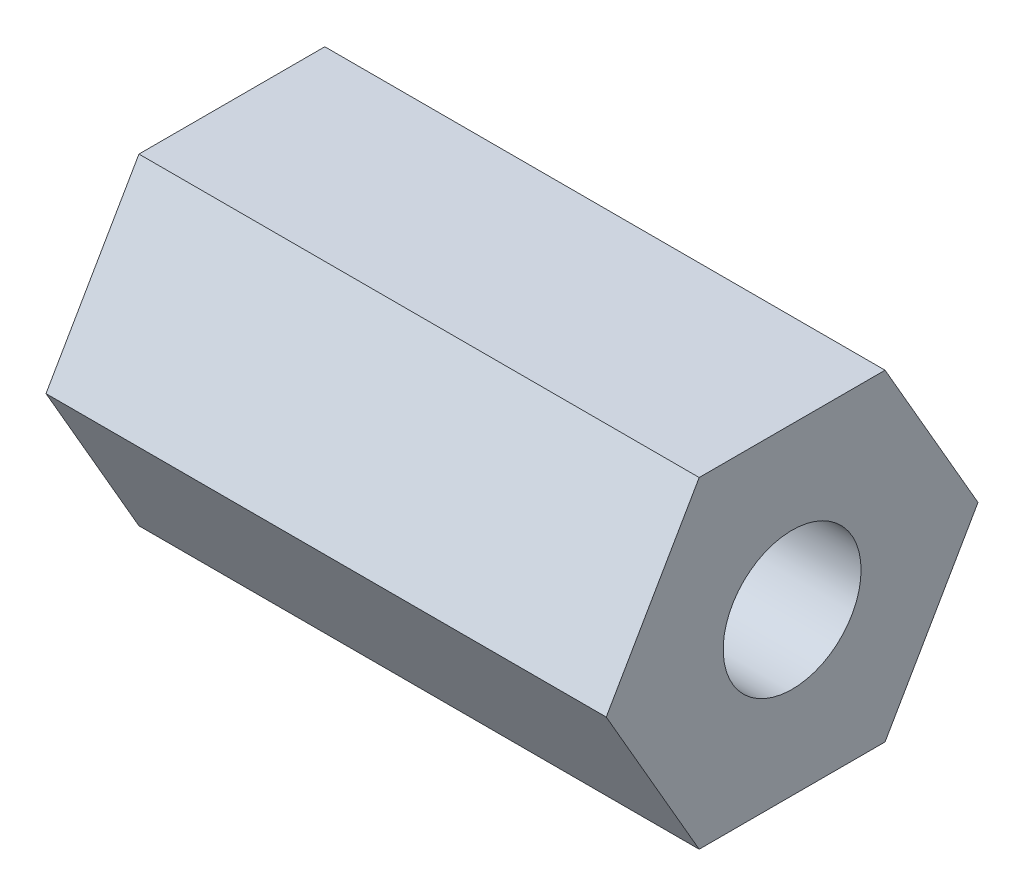
SolidWorks part; units mm, degrees
material "6061-T4 (SS)"
ref_plane "Front Plane" through (0, 0, 0) normal (0, 0, 1) x (1, 0, 0)
ref_plane "Top Plane" through (0, 0, 0) normal (0, 1, 0) x (1, 0, 0)
ref_plane "Right Plane" through (0, 0, 0) normal (1, 0, 0) x (0, 0, -1)
sketch "Sketch1" plane through (0, 0, 0) normal (1, 0, 0) x (0, 0, -1)
  line L0 (0, 0) -> (2.9445, 0) construction
  line L1 (2.9445, 0) -> (1.4722, 2.55)
  line L2 (1.4722, 2.55) -> (-1.4722, 2.55)
  line L3 (-1.4722, 2.55) -> (-2.9445, 0)
  line L4 (-2.9445, 0) -> (-1.4722, -2.55)
  line L5 (-1.4722, -2.55) -> (1.4722, -2.55)
  line L6 (1.4722, -2.55) -> (2.9445, 0)
  circle A0 centre (0, 0) radius 2.55 construction
  point P1 (-2.2084, 1.275)
  dimension "D1" = 5.1
extrude "Boss-Extrude1" add sketch "Sketch1" along normal blind 8.875
sketch "Sketch2" plane through (8.875, 0, 0) normal (1, 0, 0) x (0, 0, -1)
  circle A0 centre (0, 0) radius 1.0922
  dimension "D1" = 2.1844
extrude "Cut-Extrude1" cut sketch "Sketch2" against normal through all contours A0
